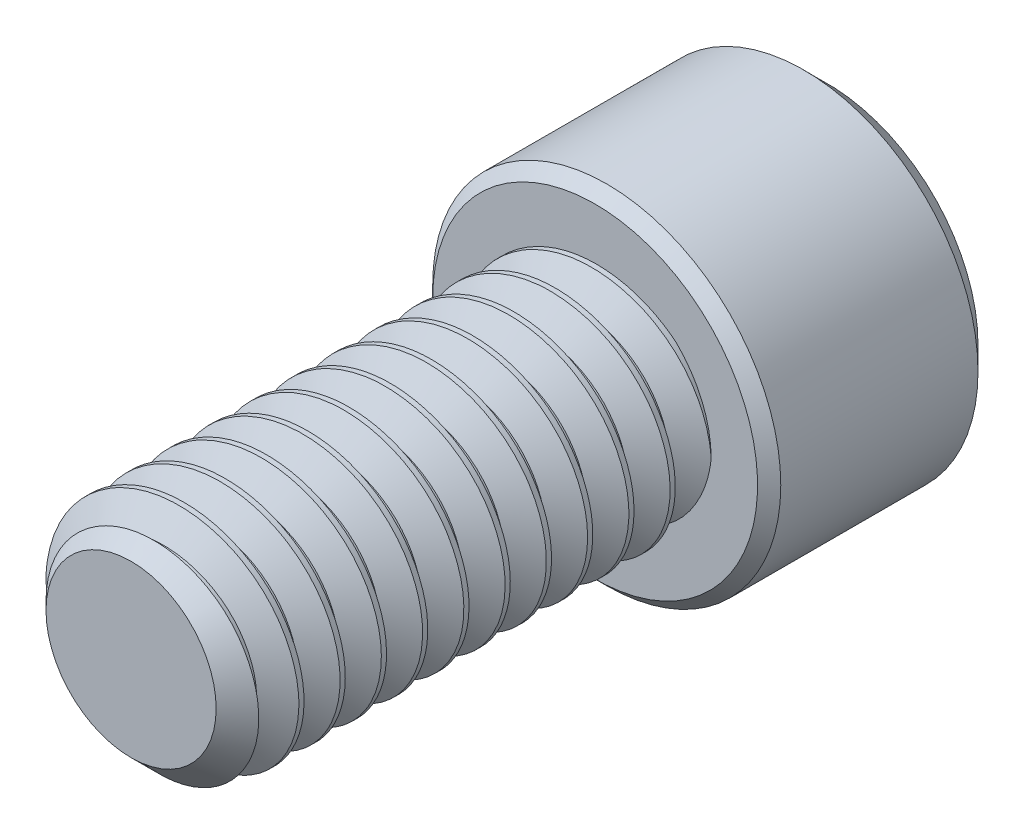
SolidWorks part; units mm, degrees
ref_plane "Front Plane" through (0, 0, 0) normal (0, 0, 1) x (1, 0, 0)
ref_plane "Top Plane" through (0, 0, 0) normal (0, 1, 0) x (1, 0, 0)
ref_plane "Right Plane" through (0, 0, 0) normal (1, 0, 0) x (0, 0, -1)
sketch "Sketch1" plane through (0, 0, 0) normal (0, 0, 1) x (1, 0, 0)
  line L0 (0, 3.9688) -> (0, -3.9688) construction
  circle A0 centre (0, 0) radius 3.9688
  dimension "OD" = 7.9375
extrude "Extrude1" add sketch "Sketch1" against normal blind 15.875
sketch "Sketch2" plane through (0, 0, 0) normal (0, 0, 1) x (1, 0, 0)
  circle A0 centre (0, 0) radius 3.9688 construction
  circle A1 centre (0, 0) radius 3.9688
curve "Helix/Spiral1" pitch 1.4111 height 17.2861 turns 12.25 parameters "pitch"=1.4111
chamfer "Chamfer3" distance 1.0583 angle 45 1 edges at (3.9688, 0, 0)
sketch "Sketch3" plane through (0, 0, 0) normal (1, 0, 0) x (0, 0, -1)
  line L0 (-1.2347, 3.9688) -> (-0.7056, 3.0522)
  line L1 (-0.7056, 3.0522) -> (-0.5292, 3.0522)
  line L2 (-0.5292, 3.0522) -> (0, 3.9688)
  line L3 (-1.2347, 3.9688) -> (0, 3.9688)
  line L4 (-0.6174, 3.9688) -> (-0.6174, 3.0522) construction
  line L5 (-0.9701, 3.5105) -> (-0.2646, 3.5105) construction
  line L6 (0, 3.9688) -> (0, -3.9688) construction
  dimension "D1" = 0.1764
  dimension "D2" = 0.7056
  dimension "D3" = 60
sweep "Cut-Sweep1" cut profiles "Sketch3" path "Helix/Spiral1"
sketch "Sketch6" plane through (0, 0, -15.875) normal (0, 0, -1) x (-1, 0, 0)
  circle A0 centre (0, 0) radius 5.9531
  dimension "head dia" = 11.9062
extrude "Extrude2" add sketch "Sketch6" along normal blind 7.9375
sketch "Sketch7" plane through (0, 0, -23.8125) normal (0, 0, -1) x (-1, 0, 0)
  line L1 (0, 3.6662) -> (-3.175, 1.8331)
  line L2 (-3.175, 1.8331) -> (-3.175, -1.8331)
  line L3 (-3.175, -1.8331) -> (0, -3.6662)
  line L4 (0, -3.6662) -> (3.175, -1.8331)
  line L5 (3.175, -1.8331) -> (3.175, 1.8331)
  line L6 (3.175, 1.8331) -> (0, 3.6662)
  circle A0 centre (0, 0) radius 3.175 construction
  dimension "hex dia" = 6.35
extrude "Cut-Extrude1" cut sketch "Sketch7" against normal blind 4.7625
sketch "Sketch8" plane through (0, 0, -23.8125) normal (0, 0, -1) x (-1, 0, 0)
  circle A0 centre (0, 0) radius 3.6662
extrude "Cut-Extrude2" cut sketch "Sketch8" against normal blind 0.7937 draft 45
chamfer "Chamfer1" distance 0.7937 angle 45 1 edges at (-5.9531, 0, -23.8125)
chamfer "Chamfer2" distance 0.3969 angle 45 1 edges at (-5.9531, 0, -15.875)
sketch "Sketch9" plane through (0, 0, 0) normal (1, 0, 0) x (0, 0, -1)
  line L0 (0, 3.9688) -> (0, -3.9688) construction
  line L1 (7.7611, 3.9688) -> (7.7611, -3.9688) construction
  line L2 (15.875, 5.9531) -> (15.875, -5.9531) construction
  line L3 (23.8125, 5.9531) -> (23.8125, -5.9531) construction
  line L4 (23.8125, 0) -> (0, 0) construction
  dimension "D1" = 7.7611
  dimension "D2" = 7.9375
  dimension "D3" = 11.9062
  dimension "D4" = 15.875
equation "\"D3@Helix/Spiral1\" = \"screw length@Extrude1\"+\"pitch@Helix/Spiral1\""
equation "\"D1@Sketch3\" = \"pitch@Helix/Spiral1\"*.125"
equation "\"D2@Sketch3\" = \"pitch@Helix/Spiral1\"*.5"
equation "\"D1@Cut-Extrude1\" = \"hex dia@Sketch7\"*.75"
equation "\"D1@Chamfer1\" = \"head depth@Extrude2\"/10"
equation "\"D1@Sketch9\" = \"pitch@Helix/Spiral1\"*5.5"
equation "\"D1@Chamfer2\" = \"D1@Chamfer1\"/2"
equation "\"D1@Cut-Extrude2\" = \"D1@Chamfer2\"*2"
equation "\"D1@Chamfer3\" = \"pitch@Helix/Spiral1\"*.750"
equation "\"D2@Sketch9\" = \"head depth@Extrude2\""
equation "\"D3@Sketch9\" = \"head dia@Sketch6\""
equation "\"D4@Sketch9\" = \"screw length@Extrude1\""
